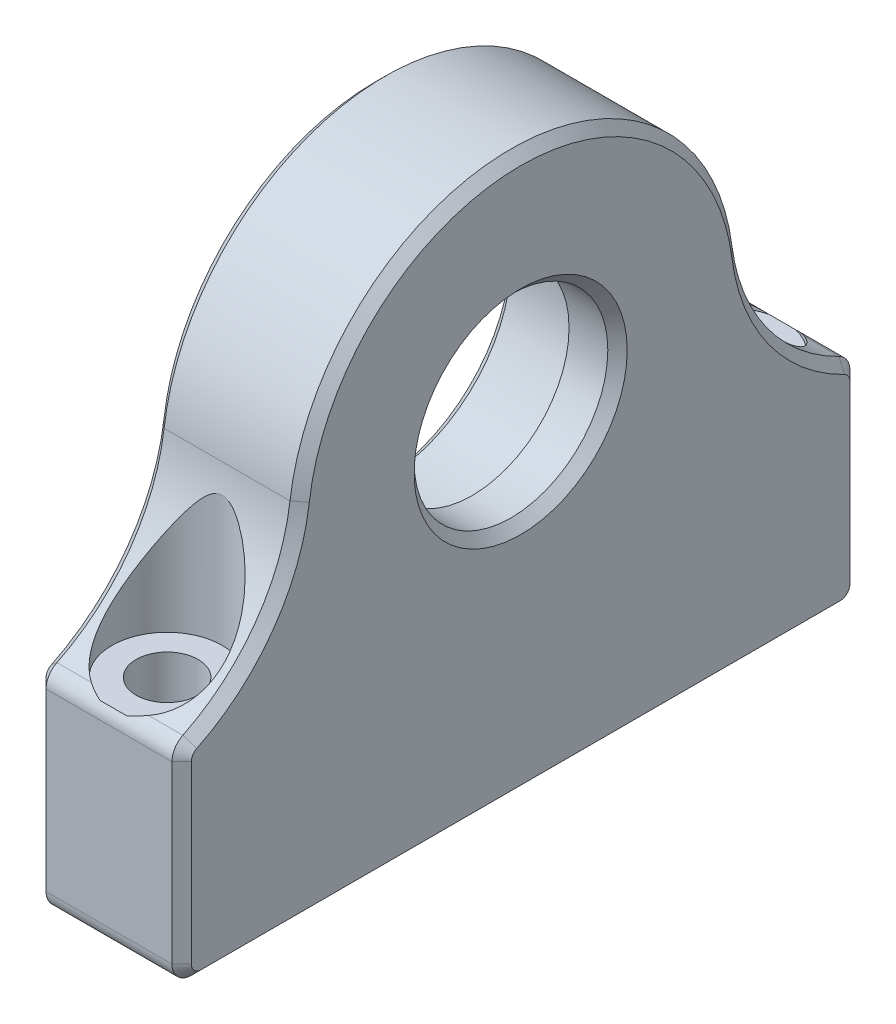
SolidWorks part; units mm, degrees
ref_plane "Front Plane" through (0, 0, 0) normal (0, 0, 1) x (1, 0, 0)
ref_plane "Top Plane" through (0, 0, 0) normal (0, 1, 0) x (1, 0, 0)
ref_plane "Right Plane" through (0, 0, 0) normal (1, 0, 0) x (0, 0, -1)
sketch "Sketch1" plane through (0, 0, 0) normal (1, 0, 0) x (0, 0, -1)
  line L0 (-9.4868, -6.5) -> (-17.5, -6.5)
  line L1 (-17.5, -6.5) -> (-17.5, -17.2)
  line L2 (-17.5, -17.2) -> (17.5, -17.2)
  line L3 (17.5, -17.2) -> (17.5, -6.5)
  line L4 (17.5, -6.5) -> (9.4868, -6.5)
  line L5 (-11.5, -997.3271) -> (-11.5, 49002.6729) construction
  circle A0 centre (0, 0) radius 6.5
  arc A1 (-9.4868, -6.5) -> (9.4868, -6.5) centre (0, 0) cw
  point P5 (0, -17.2)
  point P9 (0, -6.5)
  dimension "D1" = 13
  dimension "D2" = 5
  dimension "D3" = 17.2
  dimension "D4" = 6
extrude "Boss-Extrude1" add sketch "Sketch1" along normal mid plane 5
sketch "Sketch2" plane through (2.5, 0, 0) normal (1, 0, 0) x (0, 0, -1)
  line L5 (-9.4868, -6.5) -> (-17.5, -6.5)
  line L6 (-17.5, -6.5) -> (-17.5, -17.2)
  line L7 (-17.5, -17.2) -> (17.5, -17.2)
  line L8 (17.5, -17.2) -> (17.5, -6.5)
  line L9 (17.5, -6.5) -> (9.4868, -6.5)
  line L10 (-9.4868, -6.5) -> (-17.5, -6.5)
  line L11 (-17.5, -6.5) -> (-17.5, -17.2)
  line L12 (-17.5, -17.2) -> (17.5, -17.2)
  line L13 (17.5, -17.2) -> (17.5, -6.5)
  line L14 (17.5, -6.5) -> (9.4868, -6.5)
  circle A0 centre (0, 0) radius 5
  arc A1 (9.4868, -6.5) -> (-9.4868, -6.5) centre (0, 0) ccw
  arc A2 (9.4868, -6.5) -> (-9.4868, -6.5) centre (0, 0) ccw
  dimension "D2" = 10
  dimension "D1" = 0
extrude "Boss-Extrude2" add sketch "Sketch2" along normal blind 2.5
sketch "Sketch3" plane through (0, -6.5, 0) normal (0, 1, 0) x (1, 0, 0)
  line L0 (5, -17.5) -> (-2.5, -17.5) construction
  circle A0 centre (1.25, -14.5) radius 2.85
  point P2 (0, 0)
  point P5 (1.25, -17.5)
  dimension "D1" = 5.7
  dimension "D2" = 3
fillet "Fillet1" radius 10 2 edges at (1.25, -6.5, 9.4868) (1.25, -6.5, -9.4868)
fillet "Fillet2" radius 1 4 edges at (1.25, -17.2, 17.5) (1.25, -6.5, 17.5) (1.25, -17.2, -17.5) (1.25, -6.5, -17.5)
chamfer "Chamfer1" distance 0.5 angle 45 22 edges at (5, -17.2, 0) (5, -16.9071, -17.2071) (5, -16.9071, 17.2071) (5, -11.6729, -17.5) (5, -11.6729, 17.5) (5, -6.616, -17.3481) (5, -6.616, 17.3481) (5, -3.0891, -13.1991) (5, -3.0891, 13.1991) (5, 11.5, 0) (-2.5, -16.9071, -17.2071) (-2.5, -17.2, 0) (-2.5, -11.6729, -17.5) (-2.5, -16.9071, 17.2071) (-2.5, -6.616, -17.3481) (-2.5, -11.6729, 17.5) (-2.5, -3.0891, -13.1991) (-2.5, -6.616, 17.3481) (-2.5, 11.5, 0) (-2.5, -3.0891, 13.1991) (-2.5, 0, -6.5) (5, 0, -5)
extrude "Cut-Extrude1" cut sketch "Sketch3" along normal through all
sketch "Sketch4" plane through (0, -6.5, 0) normal (0, 1, 0) x (1, 0, 0)
  circle A0 centre (1.25, -14.5) radius 1.6
  dimension "D1" = 3.2
extrude "Cut-Extrude2" cut sketch "Sketch4" against normal through all
mirror "Mirror1" about plane through (0, 0, 0) normal (0, 0, 1) of "Cut-Extrude2", "Cut-Extrude1"
